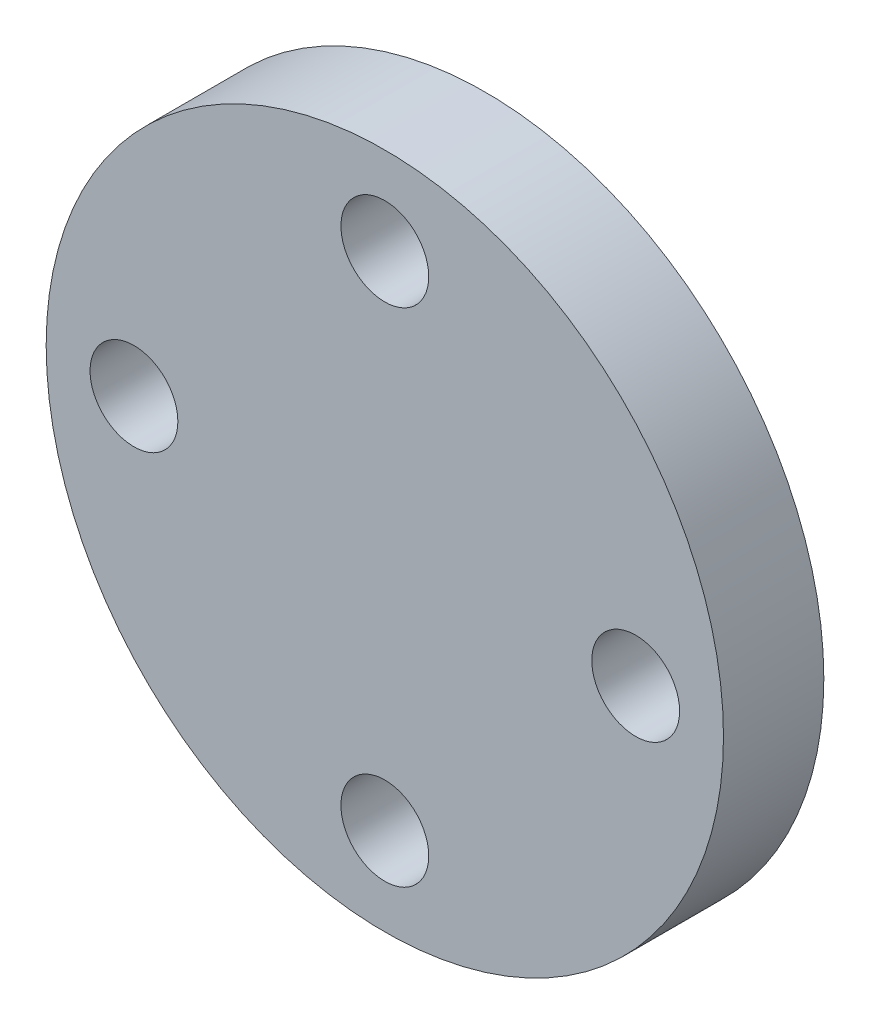
SolidWorks part; units mm, degrees
ref_plane "Front Plane" through (0, 0, 0) normal (0, 0, 1) x (1, 0, 0)
ref_plane "Top Plane" through (0, 0, 0) normal (0, 1, 0) x (1, 0, 0)
ref_plane "Right Plane" through (0, 0, 0) normal (1, 0, 0) x (0, 0, -1)
sketch "Sketch1" plane through (0, 0, 0) normal (0, 0, 1) x (1, 0, 0)
  line L0 (-10, 0) -> (0, 0) construction
  circle A0 centre (0, 0) radius 13.5
  circle A1 centre (-10, 0) radius 1.75
  circle A2 centre (0, 10) radius 1.75
  circle A3 centre (10, 0) radius 1.75
  circle A4 centre (0, -10) radius 1.75
  point P14 (0, 0)
  dimension "D1" = 27
  dimension "D3" = 3.5
  dimension "D2" = 10
  dimension "D4" = 4
extrude "Boss-Extrude1" add sketch "Sketch1" along normal blind 4
